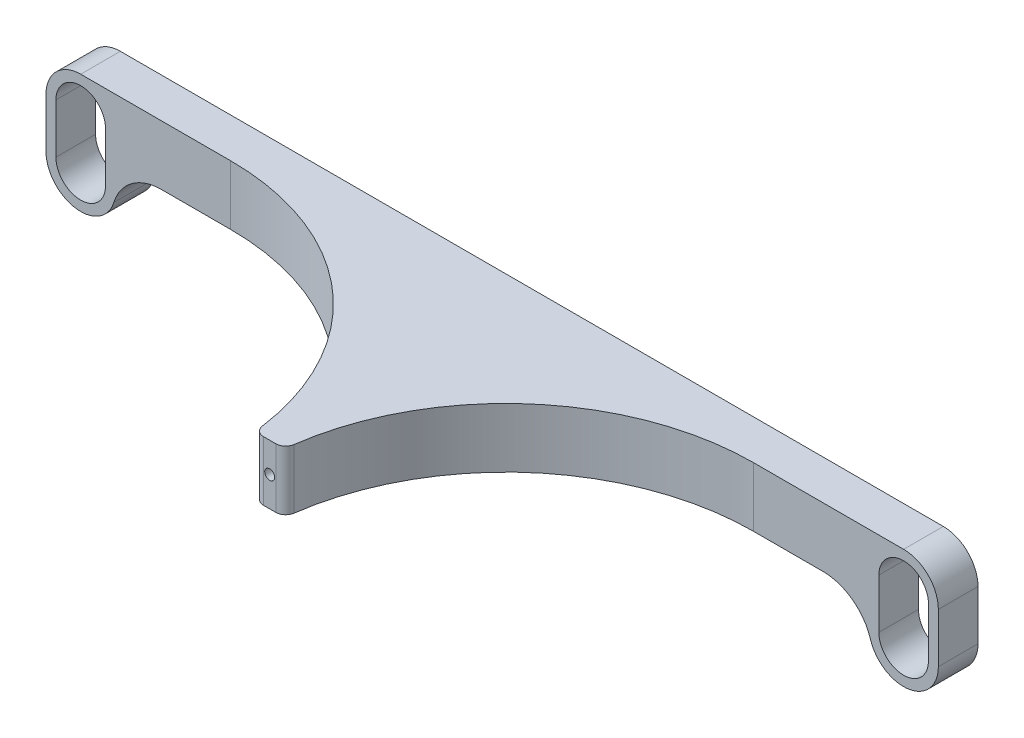
SolidWorks part; units mm, degrees
ref_plane "Alzado" through (0, 0, 0) normal (0, 0, 1) x (1, 0, 0)
ref_plane "Planta" through (0, 0, 0) normal (0, 1, 0) x (1, 0, 0)
ref_plane "Vista lateral" through (0, 0, 0) normal (1, 0, 0) x (0, 0, -1)
sketch "Croquis1" plane through (0, 0, 0) normal (0, 0, 1) x (1, 0, 0)
  line L0 (-41.5, 0) -> (41.5, 0)
  line L1 (-44, -3.5) -> (-44, -8.5)
  line L2 (-41.5, -3.5) -> (-41.5, -4.7106) construction
  line L3 (-39, -3.5) -> (-39, -8.5)
  line L4 (-45, -3.5) -> (-45, -8.5)
  line L5 (-38, -3.5) -> (-38, -8.5)
  line L6 (41.5, -3.5) -> (41.5, -4.7106) construction
  line L7 (-38, -6) -> (38, -6)
  line L8 (0, -6) -> (0, 0)
  line L9 (38, -3.5) -> (38, -8.5)
  line L10 (45, -3.5) -> (45, -8.5)
  line L11 (39, -3.5) -> (39, -8.5)
  line L12 (44, -3.5) -> (44, -8.5)
  arc A0 (-39, -3.5) -> (-44, -3.5) centre (-41.5, -3.5) ccw
  arc A1 (-44, -8.5) -> (-39, -8.5) centre (-41.5, -8.5) ccw
  arc A2 (-45, -8.5) -> (-38, -8.5) centre (-41.5, -8.5) ccw
  arc A3 (-38, -3.5) -> (-45, -3.5) centre (-41.5, -3.5) ccw
  arc A4 (38, -3.5) -> (45, -3.5) centre (41.5, -3.5) cw
  arc A5 (45, -8.5) -> (38, -8.5) centre (41.5, -8.5) cw
  arc A6 (44, -8.5) -> (39, -8.5) centre (41.5, -8.5) cw
  arc A7 (39, -3.5) -> (44, -3.5) centre (41.5, -3.5) cw
  point P4 (0, 0)
  dimension "D2" = 5
  dimension "D3" = 5
  dimension "D1" = 41.5
  dimension "D4" = 41.5
  dimension "D6" = 76
  dimension "D7" = 6
  dimension "D8" = 41.5
  dimension "D5" = 1
extrude "Saliente-Extruir1" add sketch "Croquis1" along normal blind 4 contours L5 A3 L4 A2 A1 L1 A0 L3 | A3 L5 L7 L8 L0 | L9 A4 L0 L8 L7 | A5 L10 A4 L9 L11 A7 L12 A6 region at (-19.2255, -2.9747, 0) region at (-39.1234, -1.1234, 0) region at (19.2255, -2.9747, 0) region at (43.8766, -1.1234, 0)
fillet "Redondeo1" radius 5 2 edges at (38, -6, 2) (-38, -6, 2)
sketch "Croquis2" plane through (0, 0, 4) normal (0, 0, 1) x (1, 0, 0)
  line L0 (1.5, 0) -> (-1.5, 0)
  line L1 (-41.5, 0) -> (41.5, 0) construction
  line L2 (-1.5, 0) -> (-1.5, -6)
  line L3 (-33.376, -6) -> (33.376, -6) construction
  line L4 (-1.5, -6) -> (1.5, -6)
  line L5 (1.5, -6) -> (1.5, 0)
  point P6 (0, 0)
  dimension "D1" = 3
extrude "Saliente-Extruir2" add sketch "Croquis2" along normal blind 22.44
fillet "Redondeo2" radius 25 2 edges at (1.5, -3, 4) (-1.5, -3, 4)
sketch "Croquis3" plane through (0, 0, 26.44) normal (0, 0, 1) x (1, 0, 0)
  line L0 (-1.5, -3) -> (1.5, -3) construction
  line L1 (-1.5, 0) -> (-1.5, -6) construction
  line L2 (1.5, -6) -> (1.5, 0) construction
  line L3 (1.5, -3) -> (0, 0) construction
  line L4 (0, 0) -> (0, -6) construction
  line L5 (-1.5, -6) -> (1.5, -6) construction
  circle A0 centre (0, -3) radius 0.5
  dimension "D1" = 1
extrude "Cortar-Extruir1" cut sketch "Croquis3" against normal blind 2
fillet "Redondeo3" radius 1 2 edges at (1.5, -3, 26.44) (-1.5, -3, 26.44)
